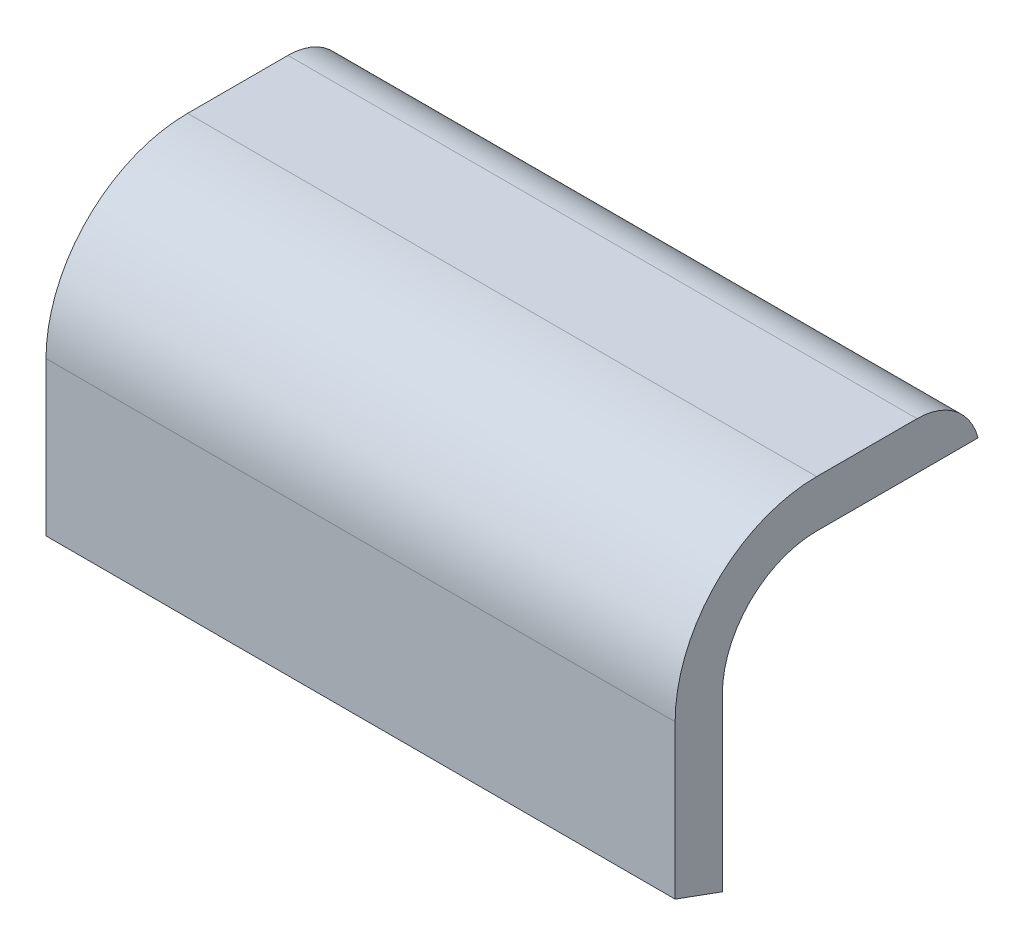
SolidWorks part; units mm, degrees
ref_plane "Front Plane" through (0, 0, 0) normal (0, 0, 1) x (1, 0, 0)
ref_plane "Top Plane" through (0, 0, 0) normal (0, 1, 0) x (1, 0, 0)
ref_plane "Right Plane" through (0, 0, 0) normal (1, 0, 0) x (0, 0, -1)
sketch "Sketch1" plane through (0, 0, 0) normal (0, 1, 0) x (1, 0, 0)
  line L1 (-50, 20.32) -> (50, 20.32)
  line L2 (-50, 20.32) -> (-50, -20.32)
  line L3 (-50, -20.32) -> (50, -20.32)
  line L4 (50, 20.32) -> (50, -20.32)
  line L5 (-50, 20.32) -> (50, -20.32) construction
  line L6 (-50, -20.32) -> (50, 20.32) construction
  point P0 (0, 0)
  dimension "D1" = 100
  dimension "D2" = 40.64
extrude "Boss-Extrude1" add sketch "Sketch1" along normal blind 7.5
sketch "Sketch2" plane through (0, 7.5, 0) normal (0, 1, 0) x (1, 0, 0)
  line L1 (-50, -20.32) -> (50, -20.32)
  line L2 (-50, -20.32) -> (-50, -27.82)
  line L3 (-50, -27.82) -> (50, -27.82)
  line L4 (50, -20.32) -> (50, -27.82)
  dimension "D1" = 7.5
extrude "Boss-Extrude2" add sketch "Sketch2" against normal blind 46.92
sketch "Sketch3" plane through (-50, 0, 0) normal (-1, 0, 0) x (0, 0, 1)
  line L0 (20.32, -39.42) -> (20.32, -42.16)
  line L1 (20.32, -42.16) -> (27.82, -39.42)
  line L2 (27.82, -39.42) -> (27.82, -32.267)
  line L3 (27.82, -39.42) -> (27.82, 7.5) construction
  line L4 (27.82, -32.267) -> (20.32, -32.267)
  line L5 (20.32, -39.42) -> (20.32, 0) construction
  line L6 (20.32, -32.267) -> (20.32, -39.42)
  dimension "D1" = 2.74
extrude "Boss-Extrude3" add sketch "Sketch3" against normal up to surface (100 mm away) up to face at (50, -10.64, 9.2733)
fillet "Fillet1" radius 10 1 edges at (0, 7.5, -20.32)
fillet "Fillet2" radius 15 1 edges at (0, 0, 20.32)
fillet "Fillet3" radius 22.5 1 edges at (0, 7.5, 27.82)
